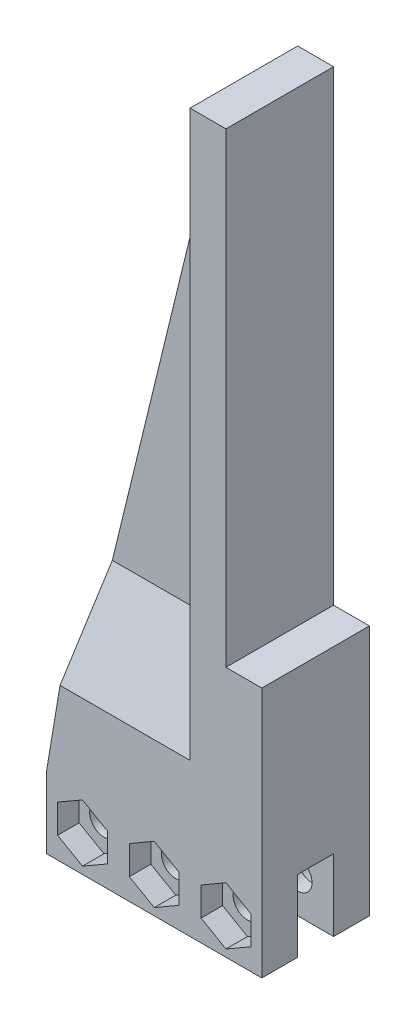
SolidWorks part; units mm, degrees
ref_plane "Front Plane" through (0, 0, 0) normal (0, 0, 1) x (1, 0, 0)
ref_plane "Top Plane" through (0, 0, 0) normal (0, 1, 0) x (1, 0, 0)
ref_plane "Right Plane" through (0, 0, 0) normal (1, 0, 0) x (0, 0, -1)
sketch "Sketch1" plane through (0, 0, 0) normal (0, 0, 1) x (1, 0, 0)
  line L0 (-25, 0) -> (-25, 10) construction
  line L1 (0, 0) -> (-30, 0)
  line L2 (0, 0) -> (0, 10)
  line L3 (0, 10) -> (-30, 10)
  line L4 (-30, 0) -> (-30, 10)
  line L5 (-5, 0) -> (-5, 10) construction
  line L6 (0, 5) -> (-30, 5) construction
  line L7 (-15, 0) -> (-15, 10) construction
  line L8 (-5, 0) -> (-5, 100)
  line L9 (0, 0) -> (-15, 0)
  line L10 (0, 0) -> (0, 100)
  line L11 (0, 100) -> (-15, 100)
  line L12 (-15, 0) -> (-15, 100)
  line L13 (0, 35) -> (-15, 35)
  line L14 (-15, 100) -> (-30, 10)
  dimension "D5" = 30
  dimension "D6" = 10
  dimension "D7" = 5
  dimension "D1" = 5
  dimension "D2" = 5
  dimension "D3" = 5
  dimension "D4" = 10
  dimension "D8" = 65
extrude "Boss-Extrude1" add sketch "Sketch1" along normal blind 15 contours L12 L14 L3 | L13 L8 L11 L12 | L8 L13 L12 L3 | L10 L13 L8 L3 | L8 L1 L2 L3 | L12 L1 L8 L3 | L1 L12 L3 L4 region at (-2.5, 5, 0) region at (-10, 5, 0) region at (-2.5, 22.5, 0) region at (-22.5, 5, 0) region at (-10, 22.5, 0) region at (-20, 40, 0) region at (-10, 67.5, 0)
hole_wizard "CBORE for M4 Hex Head Machine Screw1" positions "Sketch5" profile "Sketch4" counterbore size "M4" standard "ANSI Metric" end condition through all
sketch "Sketch5" plane through (0, 0, 0) normal (0, 0, -1) x (-1, 0, 0)
  line L0 (25, 0) -> (25, 10) construction
  line L1 (0, 5) -> (30, 5) construction
  line L2 (5, 0) -> (5, 100) construction
  point P0 (25, 5)
  point P4 (15, 5)
  point P8 (5, 5)
sketch "Sketch4" plane through (-25, 5, 0) normal (1, 0, 0) x (0, 1, 0)
  line L0 (0, 0) -> (0, 15)
  line L1 (0, 15) -> (2, 15)
  line L3 (2, 15) -> (2, 3)
  line L4 (2, 3) -> (4, 3)
  line L5 (4, 3) -> (4, 0)
  line L7 (4, 0) -> (0, 0)
  line L11 (0, -6.35) -> (0, 107.95) construction
  dimension "Thru Hole Dia." = 4
  dimension "Thru Hole Depth" = 15
  dimension "C'Bore Dia." = 8
  dimension "C'Bore Depth" = 3
sketch "Sketch6" plane through (0, 0, 15) normal (0, 0, 1) x (1, 0, 0)
  line L0 (-25, 0) -> (-25, 10) construction
  line L1 (-15, 9) -> (-18.4641, 7)
  line L2 (-25, 9) -> (-28.4641, 7)
  line L3 (-28.4641, 7) -> (-28.4641, 3)
  line L4 (-28.4641, 3) -> (-25, 1)
  line L5 (-25, 1) -> (-21.5359, 3)
  line L6 (-21.5359, 3) -> (-21.5359, 7)
  line L7 (-21.5359, 7) -> (-25, 9)
  line L8 (-18.4641, 7) -> (-18.4641, 3)
  line L9 (-18.4641, 3) -> (-15, 1)
  line L10 (-15, 1) -> (-11.5359, 3)
  line L11 (-11.5359, 3) -> (-11.5359, 7)
  line L12 (-11.5359, 7) -> (-15, 9)
  line L13 (-5, 9) -> (-8.4641, 7)
  line L14 (-8.4641, 7) -> (-8.4641, 3)
  line L15 (-8.4641, 3) -> (-5, 1)
  line L16 (-5, 1) -> (-1.5359, 3)
  line L17 (-1.5359, 3) -> (-1.5359, 7)
  line L18 (-1.5359, 7) -> (-5, 9)
  circle A0 centre (-25, 5) radius 4 construction
  circle A1 centre (-25, 5) radius 3.4641 construction
  dimension "D1" = 3
extrude "Cut-Extrude1" cut sketch "Sketch6" against normal blind 3
sketch "Sketch7" plane through (-30, 0, 0) normal (-1, 0, 0) x (0, 0, 1)
  line L0 (7.5, 10) -> (7.5, 0) construction
  line L1 (15, 10) -> (0, 10) construction
  line L2 (15, 0) -> (0, 0) construction
  line L3 (5, 10) -> (5, 0)
  line L4 (10, 10) -> (10, 0)
  line L6 (5, 10) -> (10, 10)
  line L7 (10, 0) -> (5, 0)
extrude "Cut-Extrude2" cut sketch "Sketch7" against normal through all
sketch "Sketch8" plane through (0, 0, 0) normal (0, 0, -1) x (-1, 0, 0)
  line L2 (10, 0) -> (10, 100)
  line L3 (10, 35) -> (10, 100)
  line L4 (10, 100) -> (15, 100)
  line L5 (0, 35) -> (30, 35)
  line L6 (10, 35) -> (30, 35)
  line L7 (15, 100) -> (25.8333, 35)
  line L8 (15, 100) -> (30, 10) construction
  line L9 (25.8333, 35) -> (10, 100)
  line M8 (30, 10) -> (15, 100)
  line M9 (15, 100) -> (5, 100)
  dimension "D1" = 5
  dimension "D2" = 25
extrude "Cut-Extrude3" cut sketch "Sketch8" against normal through all contours L9 M8 M9 region at (-16.9444, 78.3333, 0)
sketch "Sketch9" plane through (0, 0, 0) normal (0, 0, -1) x (-1, 0, 0)
  line L0 (10, 100) -> (10, 35)
  line L1 (0, 35) -> (15, 35) construction
  line L2 (10, 35) -> (25.8333, 35)
  line L3 (25.8333, 35) -> (10, 100)
extrude "Cut-Extrude4" cut sketch "Sketch9" against normal blind 5
sketch "Sketch10" plane through (0, 0, 15) normal (0, 0, 1) x (1, 0, 0)
  line L0 (-10, 100) -> (-10, 35)
  line L1 (-10, 35) -> (-25.8333, 35)
  line L2 (-25.8333, 35) -> (-10, 100)
extrude "Cut-Extrude5" cut sketch "Sketch10" against normal blind 5
chamfer "Chamfer1" distance 5 angle 70 1 edges at (-17.9167, 35, 15) first distance on face at (-17.9167, 35, 12.5)
chamfer "Chamfer2" distance 5 angle 70 1 edges at (-17.9167, 35, 0) first distance on face at (-17.9167, 35, 2.5)
